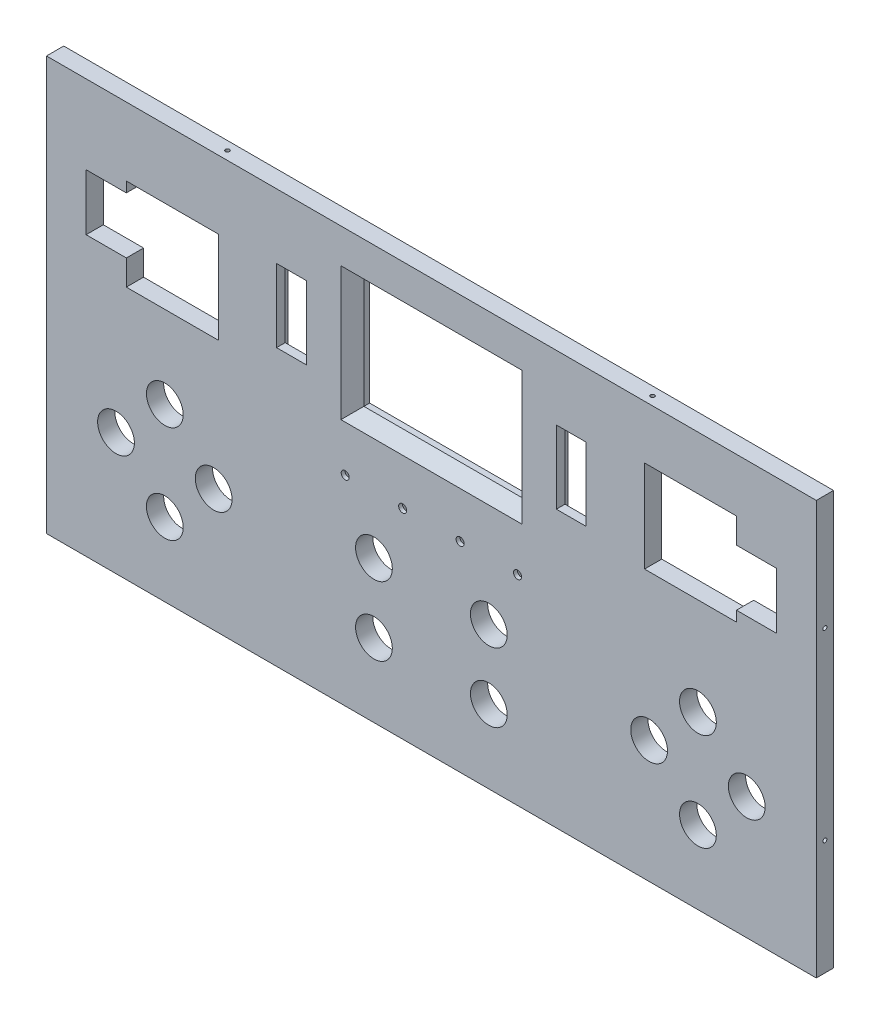
SolidWorks part; units mm, degrees
ref_plane "前视基准面" through (0, 0, 0) normal (0, 0, 1) x (1, 0, 0)
ref_plane "上视基准面" through (0, 0, 0) normal (0, 1, 0) x (1, 0, 0)
ref_plane "右视基准面" through (0, 0, 0) normal (1, 0, 0) x (0, 0, -1)
other "Configuration Table"
sketch "草图1" plane through (0, 0, 0) normal (0, 0, 1) x (1, 0, 0)
  line L1 (-70, 40) -> (70, 40)
  line L2 (-70, 40) -> (-70, -40)
  line L3 (-70, -40) -> (70, -40)
  line L4 (70, 40) -> (70, -40)
  point P4 (0, 40)
  point P6 (-70, 0)
  dimension "D1" = 140
  dimension "D2" = 80
extrude "凸台-拉伸1" add sketch "草图1" along normal blind 3
sketch "草图2" plane through (0, 0, 3) normal (0, 0, 1) x (1, 0, 0)
  line L1 (-13.75, 24) -> (13.75, 24)
  line L2 (-13.75, 24) -> (-13.75, 4.8)
  line L3 (-13.75, 4.8) -> (13.75, 4.8)
  line L4 (13.75, 24) -> (13.75, 4.8)
  line L5 (70, 40) -> (-70, 40) construction
  point P4 (0, 24)
  dimension "D1" = 27.5
  dimension "D2" = 19.2
  dimension "D3" = 16
extrude "切除-拉伸1" cut sketch "草图2" against normal through all
ref_plane "基准面1" through (0, -5.2, 0) normal (0, 1, 0) x (1, 0, 0)
chamfer "倒角1" distance 2 angle 45 4 edges at (13.75, 14.4, 3) (0, 24, 3) (0, 4.8, 3) (-13.75, 14.4, 3)
sketch "草图16" plane through (0, 0, 0) normal (0, 0, -1) x (-1, 0, 0)
  line L0 (-13.75, 24) -> (13.75, 24) construction
  line L1 (-8.89, 27.34) -> (8.89, 27.34)
  line L2 (-8.89, 27.34) -> (-8.89, 24.8)
  line L3 (-8.89, 24.8) -> (8.89, 24.8)
  line L4 (8.89, 27.34) -> (8.89, 24.8)
  point P7 (0, 24.8)
  dimension "D1" = 0.8
  dimension "D2" = 2.54
  dimension "D3" = 17.78
extrude "切除-拉伸15" cut sketch "草图16" against normal blind 1
sketch "草图3" plane through (0, -5.2, 0) normal (0, 1, 0) x (1, 0, 0)
  line L0 (-15, 6.0122) -> (-15, -8.0142) construction
  line L1 (-15, -3) -> (-14.3, -3)
  line L2 (-15, -3) -> (-15, -2)
  line L3 (-15, -2) -> (-14.3, -2)
  line L4 (-14.3, -3) -> (-14.3, -2)
  line L5 (-5, 6.4208) -> (-5, -10.2476) construction
  line L6 (5, -10.0569) -> (5, -6.8431) construction
  line L7 (15, -4.2829) -> (15, -10.4382) construction
  line L8 (-15, -5.6016) -> (-5, -5.6016)
  line L9 (-5, -5.6016) -> (5, -5.6016)
  line L10 (5, -5.6016) -> (15, -5.6016)
  line L11 (70, -3) -> (-70, -3) construction
  line L12 (-15, 0.7) -> (-15, -2)
  line L13 (-5, -3) -> (-4.3, -3)
  line L14 (-5, -3) -> (-5, -2)
  line L15 (-5, -2) -> (-4.3, -2)
  line L16 (-4.3, -3) -> (-4.3, -2)
  line L17 (5, -3) -> (5.7, -3)
  line L18 (5, -3) -> (5, -2)
  line L19 (5, -2) -> (5.7, -2)
  line L20 (5.7, -3) -> (5.7, -2)
  line L21 (15, -3) -> (15.7, -3)
  line L22 (15, -3) -> (15, -2)
  line L23 (15, -2) -> (15.7, -2)
  line L24 (15.7, -3) -> (15.7, -2)
  line L25 (-5, 0.7) -> (-5, -2)
  line L26 (5, 0.7) -> (5, -2)
  line L27 (15, 0.7) -> (15, -2)
  line L28 (-16.6, -0.9) -> (-16.6, 0)
  line L29 (70, 0) -> (-70, 0) construction
  line L30 (-13.4, -0.9) -> (-13.4, 0)
  line L31 (-6.6, -0.9) -> (-6.6, 0)
  line L32 (-3.4, -0.9) -> (-3.4, 0)
  line L33 (3.4, -0.9) -> (3.4, 0)
  line L34 (6.6, -0.9) -> (6.6, 0)
  line L35 (13.4, -0.9) -> (13.4, 0)
  line L36 (16.6, -0.9) -> (16.6, 0)
  line L37 (-16.6, 0) -> (16.6, 0)
  circle A0 centre (-15, -0.9) radius 1.6
  circle A1 centre (-5, -0.9) radius 1.6
  circle A2 centre (5, -0.9) radius 1.6
  circle A3 centre (15, -0.9) radius 1.6
  point P14 (0, -5.6016)
  point P34 (-15, -2.5)
  dimension "D4" = 3.2
  dimension "D1" = 10
  dimension "D2" = 1
  dimension "D3" = 0.7
revolve "切除-旋转4" cut sketch "草图3" angle 360 about L0 region at (-14.6332, -5.2, 2.7216) region at (-14.6708, -5.2, 2.2262) region at (-14.2501, -5.2, 1.0166) region at (-13.4817, -5.2, 0.2209)
revolve "切除-旋转5" cut sketch "草图3<6>" angle 360 about L5 region at (-4.6332, -5.2, 2.7216) region at (-4.6708, -5.2, 2.2262) region at (-4.2501, -5.2, 1.0166) region at (-3.4817, -5.2, 0.2209)
sketch "草图3<6>" plane through (0, -5.2, 0) normal (0, 1, 0) x (1, 0, 0) same geometry as "草图3"
revolve "切除-旋转6" cut sketch "草图3<7>" angle 360 about L6 region at (5.3668, -5.2, 2.7216) region at (5.3292, -5.2, 2.2262) region at (5.7499, -5.2, 1.0166) region at (6.5183, -5.2, 0.2209)
sketch "草图3<7>" plane through (0, -5.2, 0) normal (0, 1, 0) x (1, 0, 0) same geometry as "草图3"
revolve "切除-旋转7" cut sketch "草图3<8>" angle 360 about L7 region at (15.3668, -5.2, 2.7216) region at (15.3292, -5.2, 2.2262) region at (15.7499, -5.2, 1.0166) region at (16.5183, -5.2, 0.2209)
sketch "草图3<8>" plane through (0, -5.2, 0) normal (0, 1, 0) x (1, 0, 0) same geometry as "草图3"
sketch "草图5" plane through (0, 0, 3) normal (0, 0, 1) x (1, 0, 0)
  line L0 (-13.75, 24) -> (-13.75, 4.8) construction
  line L1 (-26.95, 20.75) -> (-21.75, 20.75)
  line L2 (-26.95, 20.75) -> (-26.95, 8.05)
  line L3 (-26.95, 8.05) -> (-21.75, 8.05)
  line L4 (-21.75, 20.75) -> (-21.75, 8.05)
  line L7 (-27.95, 23.4) -> (-20.75, 23.4)
  line L8 (-27.95, 23.4) -> (-27.95, 5.4)
  line L9 (-27.95, 5.4) -> (-20.75, 5.4)
  line L10 (-20.75, 23.4) -> (-20.75, 5.4)
  line L11 (13.75, 4.8) -> (13.75, 24) construction
  line L12 (21.75, 8.05) -> (26.95, 8.05)
  line L13 (21.75, 8.05) -> (21.75, 20.75)
  line L14 (21.75, 20.75) -> (26.95, 20.75)
  line L15 (26.95, 8.05) -> (26.95, 20.75)
  line L16 (20.75, 5.4) -> (27.95, 5.4)
  line L17 (20.75, 5.4) -> (20.75, 23.4)
  line L18 (20.75, 23.4) -> (27.95, 23.4)
  line L19 (27.95, 5.4) -> (27.95, 23.4)
  point P6 (-13.75, 14.4)
  point P7 (-21.75, 14.4)
  point P10 (-24.35, 20.75)
  point P16 (-27.95, 14.4)
  point P17 (-26.95, 14.4)
  point P18 (-24.35, 23.4)
  point P26 (21.75, 14.4)
  point P27 (20.75, 14.4)
  point P28 (24.35, 20.75)
  point P29 (24.35, 23.4)
  dimension "D1" = 5.2
  dimension "D2" = 12.7
  dimension "D3" = 7.2
  dimension "D4" = 18
  dimension "D5" = 8
  dimension "D6" = 8
extrude "切除-拉伸3" cut sketch "草图5" against normal through all contours L9 L10 L7 L8 | L16 L19 L18 L17
extrude "凸台-拉伸2" add sketch "草图5<4>" against normal blind 1.5 contours L10 L9 L8 L7 | L4 L3 L2 L1 | L16 L19 L18 L17 | L12 L15 L14 L13
sketch "草图5<4>" plane through (0, 0, 3) normal (0, 0, 1) x (1, 0, 0) same geometry as "草图5"
sketch "草图7" plane through (0, 0, 3) normal (0, 0, 1) x (1, 0, 0)
  line L0 (-46.4, -10.2) -> (-46.4, -27.2)
  line L1 (37.9, -18.7) -> (54.9, -18.7)
  line L2 (-54.9, -18.7) -> (-37.9, -18.7)
  line L3 (-10, -15.2) -> (10, -15.2)
  line L4 (-37.9, -18.7) -> (37.9, -18.7)
  line L6 (-70, 40) -> (-70, -40) construction
  line L8 (-15, -5.2) -> (15, -5.2)
  line L9 (-10, -15.2) -> (-10, -5.2)
  line L10 (0, 4.8) -> (0, -5.2)
  line L11 (-13.75, 4.8) -> (13.75, 4.8) construction
  circle A0 centre (-46.4, -10.2) radius 3.2
  circle A1 centre (-46.4, -27.2) radius 3.2
  circle A2 centre (-54.9, -18.7) radius 3.2
  circle A3 centre (-37.9, -18.7) radius 3.2
  circle A4 centre (-10, -15.2) radius 3.2
  circle A5 centre (10, -15.2) radius 3.2
  circle A6 centre (-10, -27.2) radius 3.2
  circle A7 centre (10, -27.2) radius 3.2
  circle A8 centre (46.4, -10.2) radius 3.2
  circle A9 centre (37.9, -18.7) radius 3.2
  circle A10 centre (54.9, -18.7) radius 3.2
  circle A11 centre (46.4, -27.2) radius 3.2
  circle A12 centre (-15, -5.2) radius 0.7 construction
  circle A13 centre (15, -5.2) radius 0.7 construction
  point P24 (-46.4, -18.7)
  point P25 (0, -15.2)
  point P26 (46.4, -18.7)
  point P27 (-46.4, -18.7)
  point P28 (0, -18.7)
  dimension "D1" = 6.4
  dimension "D2" = 12
  dimension "D3" = 17
  dimension "D4" = 23.6
  dimension "D5" = 20
extrude "切除-拉伸5" cut sketch "草图7" against normal through all contours A0 | A2 | A1 | A3 | A6 | A4 | A5 | A7 | A9 | A8 | A10 | A11
sketch "草图8" plane through (0, 0, 3) normal (0, 0, 1) x (1, 0, 0)
  line L1 (-60.1, 18.3) -> (-53.1, 18.3)
  line L2 (-60.1, 18.3) -> (-60.1, 8.5)
  line L3 (-60.1, 8.5) -> (-53.1, 8.5)
  line L4 (-53.1, 18.3) -> (-53.1, 8.5)
  line L5 (-70, 40) -> (-70, -40) construction
  line L6 (-53.1, 20.1) -> (-37.1, 20.1)
  line L7 (-53.1, 20.1) -> (-53.1, 4.1)
  line L8 (-53.1, 4.1) -> (-37.1, 4.1)
  line L9 (-37.1, 20.1) -> (-37.1, 4.1)
  line L10 (70, 40) -> (-70, 40) construction
  line L11 (70, -40) -> (70, 40) construction
  line L20 (53.1, 6.7) -> (37.1, 6.7)
  line L21 (53.1, 6.7) -> (53.1, 22.7)
  line L22 (53.1, 22.7) -> (37.1, 22.7)
  line L23 (37.1, 6.7) -> (37.1, 22.7)
  line L24 (53.1, 18.3) -> (60.1, 18.3)
  line L25 (53.1, 18.3) -> (53.1, 8.5)
  line L26 (53.1, 8.5) -> (60.1, 8.5)
  line L27 (60.1, 18.3) -> (60.1, 8.5)
  point P38 (-37.2505, 4.1)
  point P39 (-35.8851, 4.1)
  dimension "D1" = 9.9
  dimension "D2" = 19.9
  dimension "D3" = 16
  dimension "D4" = 7
  dimension "D5" = 1.8
  dimension "D6" = 9.8
  dimension "D11" = 9.9
  dimension "D12" = 17.3
extrude "切除-拉伸6" cut sketch "草图8" against normal through all contours L3 L4 L1 L2 | L8 L9 L6 L7 | L26 L27 L24 L25 | L20 L23 L22 L21
sketch "草图9" plane through (0, 0, 0) normal (0, 0, -1) x (-1, 0, 0)
  circle A0 centre (-61.65, 21.2) radius 0.35
  circle A1 centre (-61.65, 5.6) radius 0.35
  circle A2 centre (-35.55, 21.2) radius 0.35
  circle A3 centre (-35.55, 5.6) radius 0.35
  circle A4 centre (-24.35, 24.9) radius 0.35
  circle A5 centre (-24.35, 3.9) radius 0.35
  circle A6 centre (-17.35, 26.65) radius 0.35
  circle A7 centre (-17.35, 2.15) radius 0.35
  circle A8 centre (17.35, 26.65) radius 0.35
  circle A9 centre (17.35, 2.15) radius 0.35
  circle A10 centre (24.35, 24.9) radius 0.35
  circle A11 centre (24.35, 3.9) radius 0.35
  circle A12 centre (35.55, 21.2) radius 0.35
  circle A13 centre (35.55, 5.6) radius 0.35
  circle A14 centre (61.65, 21.2) radius 0.35
  circle A15 centre (61.65, 5.6) radius 0.35
  circle A16 centre (46.4, -2.1) radius 0.35
  circle A17 centre (29.8, -18.7) radius 0.35
  circle A18 centre (46.4, -35.3) radius 0.35
  circle A19 centre (63, -18.7) radius 0.35
  circle A20 centre (-21.225, -5.2) radius 0.35
  circle A21 centre (0, -1.2) radius 0.35
  circle A22 centre (0, -9.2) radius 0.35
  circle A23 centre (21.225, -5.2) radius 0.35
  circle A24 centre (-18.1, -15.2) radius 0.35
  circle A25 centre (-18.1, -27.2) radius 0.35
  circle A26 centre (-3.5, -21.2) radius 0.35
  circle A27 centre (3.5, -21.2) radius 0.35
  circle A28 centre (18.1, -15.2) radius 0.35
  circle A29 centre (18.1, -27.2) radius 0.35
  circle A30 centre (-46.4, -2.1) radius 0.35
  circle A31 centre (-29.8, -18.7) radius 0.35
  circle A32 centre (-46.4, -35.3) radius 0.35
  circle A33 centre (-63, -18.7) radius 0.35
  dimension "D1" = 0.7
extrude "切除-拉伸7" cut sketch "草图9" against normal blind 1.5
sketch "草图12" plane through (0, 0, 3) normal (0, 0, 1) x (1, 0, 0)
  line L0 (70, -40) -> (70, 40) construction
  line L1 (-70, 40) -> (70, 40)
  line L2 (-70, 40) -> (-70, 32)
  line L3 (-70, 32) -> (70, 32)
  line L4 (70, 40) -> (70, 32)
  line L5 (-70, -40) -> (70, -40) construction
  line L6 (-67, 32) -> (-70, 32)
  line L7 (-67, 32) -> (-67, -40)
  line L8 (-67, -40) -> (-70, -40)
  line L9 (-70, 32) -> (-70, -40)
  line L11 (70, -40) -> (67, -40)
  line L12 (70, -40) -> (70, 32)
  line L13 (70, 32) -> (67, 32)
  line L14 (67, -40) -> (67, 32)
  dimension "D1" = 8
  dimension "D2" = 3
extrude "切除-拉伸9" cut sketch "草图12" against normal through all contours L3 L4 L1 L2 | L9 L8 L7 L6 | L12 L11 L14 L13
sketch "草图13" plane through (0, 32, 0) normal (0, 1, 0) x (1, 0, 0)
  line L0 (-37, -1.5) -> (37, -1.5)
  line L1 (-67, 0) -> (-67, -3) construction
  circle A0 centre (-37, -1.5) radius 0.35
  circle A1 centre (37, -1.5) radius 0.35
  point P4 (0, -1.5)
  point P8 (-67, -1.5)
  dimension "D1" = 0.7
  dimension "D2" = 30
extrude "切除-拉伸10" cut sketch "草图13" against normal blind 1.5 contours A0 | A1
sketch "草图14" plane through (0, 0, 0) normal (0, 0, -1) x (-1, 0, 0)
  line L0 (-39, -5) -> (-28, -5)
  line L1 (-28, -5) -> (0, -5)
  line L2 (0, -5) -> (28, -5)
  line L3 (28, -5) -> (39, -5)
  circle A0 centre (-39, -5) radius 0.35
  circle A1 centre (-28, -5) radius 0.35
  circle A2 centre (28, -5) radius 0.35
  circle A3 centre (39, -5) radius 0.35
  dimension "D1" = 0.7
  dimension "D2" = 28
  dimension "D3" = 11
  dimension "D4" = 5
extrude "切除-拉伸11" cut sketch "草图14" against normal blind 1.5 contours A0 | A1 | A2 | A3
extrude "切除-拉伸12" cut sketch "草图13<3>" along normal blind 1.5 from surface contours A0 | A1 starting at face at (0, -40, 1.5)
sketch "草图13<3>" plane through (0, 32, 0) normal (0, 1, 0) x (1, 0, 0) same geometry as "草图13"
sketch "草图15" plane through (67, 0, 0) normal (1, 0, 0) x (0, 0, -1)
  line L0 (-1.5, 12) -> (-1.5, -4)
  line L1 (-1.5, -4) -> (-1.5, -20)
  line L2 (0, 32) -> (-3, 32) construction
  line L3 (-3, -40) -> (-3, 32) construction
  circle A0 centre (-1.5, 12) radius 0.35
  circle A1 centre (-1.5, -20) radius 0.35
  point P11 (-1.5, 32)
  point P12 (-3, -4)
  dimension "D1" = 0.7
  dimension "D2" = 20
extrude "切除-拉伸13" cut sketch "草图15" against normal blind 1.5 contours A1 | A0
extrude "切除-拉伸14" cut sketch "草图15<3>" along normal blind 1.5 from surface contours A1 | A0 starting at face at (-67, -4, 1.5)
sketch "草图15<3>" plane through (67, 0, 0) normal (1, 0, 0) x (0, 0, -1) same geometry as "草图15"
